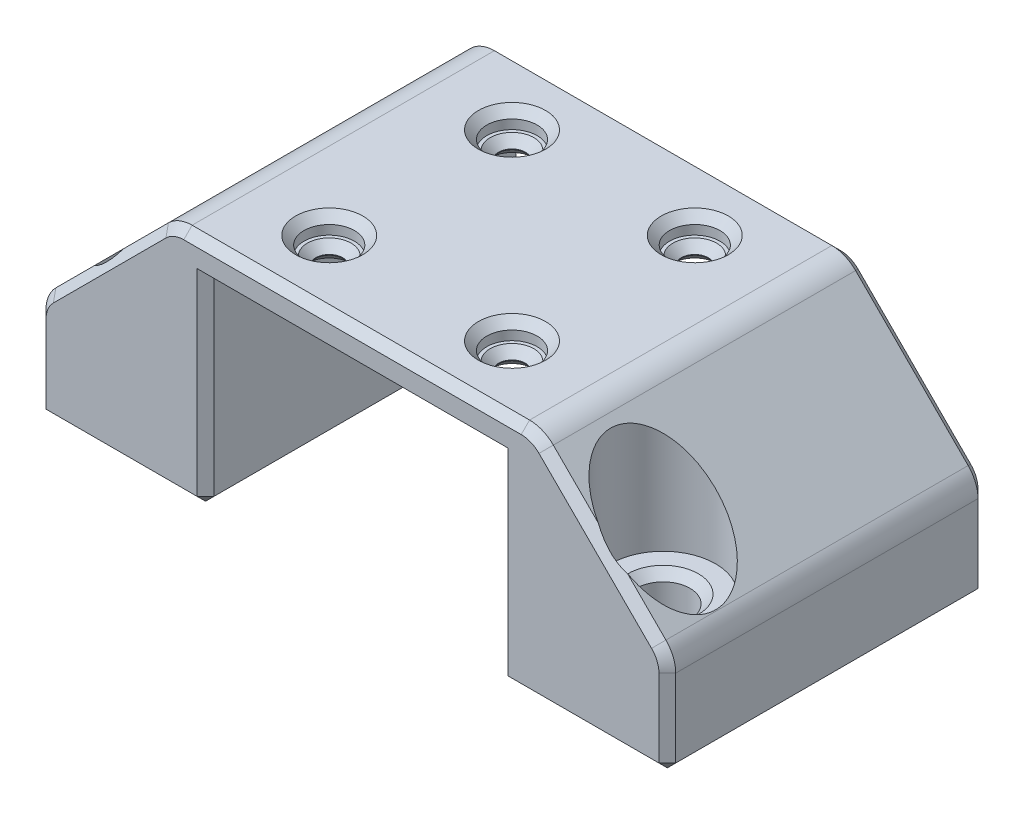
SolidWorks part; units mm, degrees
ref_plane "Front Plane" through (0, 0, 0) normal (0, 0, 1) x (1, 0, 0)
ref_plane "Top Plane" through (0, 0, 0) normal (0, 1, 0) x (1, 0, 0)
ref_plane "Right Plane" through (0, 0, 0) normal (1, 0, 0) x (0, 0, -1)
sketch "Sketch1" plane through (0, 0, 0) normal (0, 0, 1) x (1, 0, 0)
  line L0 (0, -12.67) -> (0, 30.502) construction
  line L1 (-11.1125, 0) -> (-11.1125, 14.9225)
  line L2 (-11.1125, 0) -> (-23.8125, 0)
  line L3 (-11.1125, 14.9225) -> (11.1125, 14.9225)
  line L4 (-23.8125, 17.5746) -> (23.8125, 17.5746)
  line L5 (-23.8125, 0) -> (-23.8125, 17.5746)
  line L6 (11.1125, 0) -> (23.8125, 0)
  line L7 (23.8125, 0) -> (23.8125, 17.5746)
  line L8 (11.1125, 0) -> (11.1125, 14.9225)
  point P9 (0, 17.5746)
  point P13 (0, 14.9225)
  dimension "D1" = 12.7
  dimension "D2" = 11.1125
  dimension "D3" = 14.9225
  dimension "D4" = 17.5746
extrude "Boss-Extrude1" add sketch "Sketch1" along normal blind 24.13
chamfer "Chamfer1" distance 10 angle 45 2 edges at (23.8125, 17.5746, 12.065) (-23.8125, 17.5746, 12.065)
fillet "Fillet1" radius 2.54 2 edges at (13.8125, 17.5746, 12.065) (-13.8125, 17.5746, 12.065)
fillet "Fillet2" radius 2.54 2 edges at (23.8125, 7.5746, 12.065) (-23.8125, 7.5746, 12.065)
sketch "Sketch2" plane through (0, 0, 0) normal (0, -1, 0) x (1, 0, 0)
  line L0 (0, -12.2519) -> (0, 31.6273) construction
  line L1 (-35.4754, 12.065) -> (35.4754, 12.065) construction
  line L2 (-11.1125, 0) -> (11.1125, 0) construction
  circle A0 centre (-19.05, 19.685) radius 2.032
  circle A1 centre (19.05, 19.685) radius 2.032
  dimension "D1" = 4.064
  dimension "D2" = 7.62
  dimension "D3" = 12.065
  dimension "D4" = 19.05
extrude "Cut-Extrude1" cut sketch "Sketch2" against normal blind 10.16
sketch "Sketch3" plane through (0, 17.5746, 0) normal (0, 1, 0) x (1, 0, 0)
  line L0 (0, 9.1955) -> (0, -28.8887) construction
  line L1 (-14.5564, -12.065) -> (14.5564, -12.065) construction
  line L2 (-14.5564, -24.13) -> (-14.5564, 0) construction
  line L3 (14.5564, 0) -> (14.5564, -24.13) construction
  circle A0 centre (-6.9113, -5.1537) radius 1.016
  circle A1 centre (6.9113, -5.1537) radius 1.016
  circle A2 centre (6.9113, -18.9763) radius 1.016
  circle A3 centre (-6.9113, -18.9763) radius 1.016
  dimension "D3" = 2.032
  dimension "D1" = 6.9113
  dimension "D2" = 6.9113
extrude "Cut-Extrude2" cut sketch "Sketch3" against normal through all
sketch "Sketch4" plane through (0, 17.5746, 0) normal (0, 1, 0) x (1, 0, 0)
  line L0 (0, 10.8653) -> (0, -31.1365) construction
  line L1 (-14.5564, -12.065) -> (14.5564, -12.065) construction
  line L2 (-14.5564, -24.13) -> (-14.5564, 0) construction
  line L3 (14.5564, 0) -> (14.5564, -24.13) construction
  circle A0 centre (-6.9113, -5.1537) radius 1.905
  circle A1 centre (6.9113, -5.1537) radius 1.905
  circle A2 centre (6.9113, -18.9763) radius 1.905
  circle A3 centre (-6.9113, -18.9763) radius 1.905
  dimension "D1" = 3.81
extrude "Cut-Extrude3" cut sketch "Sketch4" against normal blind 1.3335
sketch "Sketch5" plane through (0, 0, 0) normal (0, -1, 0) x (1, 0, 0)
  line L0 (0, 26.4248) -> (0, -11.0183) construction
  line L1 (-23.8125, 12.065) -> (23.8125, 12.065) construction
  line L2 (-23.8125, 24.13) -> (-23.8125, 0) construction
  line L3 (23.8125, 24.13) -> (23.8125, 0) construction
  circle A0 centre (-19.05, 4.445) radius 2.032
  circle A2 centre (19.05, 4.445) radius 2.032
  dimension "D3" = 4.064
  dimension "D1" = 7.62
  dimension "D2" = 19.05
extrude "Cut-Extrude4" cut sketch "Sketch5" against normal blind 8.89
sketch "Sketch7" plane through (0, 17.5746, 0) normal (0, 1, 0) x (1, 0, 0)
  line L0 (0, 10.3263) -> (0, -35.1994) construction
  line L1 (-23.8125, -12.065) -> (23.8125, -12.065) construction
  line L2 (-23.8125, -24.13) -> (-23.8125, 0) construction
  line L3 (23.8125, 0) -> (23.8125, -24.13) construction
  circle A2 centre (19.05, -19.685) radius 3.9688
  circle A3 centre (-19.05, -19.685) radius 3.9688
extrude "Cut-Extrude5" cut sketch "Sketch7" against normal blind 10.16
chamfer "Chamfer2" distance 0.635 angle 45 50 edges at (19.05, 7.4146, 17.653) (11.1125, 0, 12.065) (17.4625, 0, 24.13) (23.8125, 0, 12.065) (17.4625, 0, 0) (17.018, 0, 19.685) (17.018, 0, 4.445) (-11.1125, 7.4613, 24.13) (-11.1125, 7.4613, 0) (11.1125, 7.4613, 24.13) (11.1125, 7.4613, 0) (0, 14.9225, 24.13) (0, 14.9225, 0) (-6.9113, 14.9225, 6.1697) (6.9113, 14.9225, 6.1697) (6.9113, 14.9225, 19.9923) (-6.9113, 14.9225, 19.9923) (23.8125, 3.2613, 0) (-23.8125, 3.2613, 0) (23.6192, 7.4945, 0) (-23.6192, 7.4945, 0) (18.8125, 12.5746, 0) (-18.8125, 12.5746, 0) (13.7324, 17.3813, 0) (-13.7324, 17.3813, 0) (0, 17.5746, 0) (23.8125, 3.2613, 24.13) (-23.8125, 3.2613, 24.13) (23.6192, 7.4945, 24.13) (-23.6192, 7.4945, 24.13) (18.8125, 12.5746, 24.13) (-18.8125, 12.5746, 24.13) (13.7324, 17.3813, 24.13) (-13.7324, 17.3813, 24.13) (0, 17.5746, 24.13) (-6.9113, 17.5746, 7.0587) (6.9113, 17.5746, 3.2487) (6.9113, 17.5746, 20.8813) (-6.9113, 17.5746, 17.0713) (-19.05, 7.4146, 21.717) (-23.8125, 0, 12.065) (-17.4625, 0, 24.13) (-11.1125, 0, 12.065) (-17.4625, 0, 0) (-17.018, 0, 19.685) (-17.018, 0, 4.445) (6.9113, 16.2411, 4.1377) (-6.9113, 16.2411, 6.1697) (-6.9113, 16.2411, 17.9603) (6.9113, 16.2411, 19.9923)
